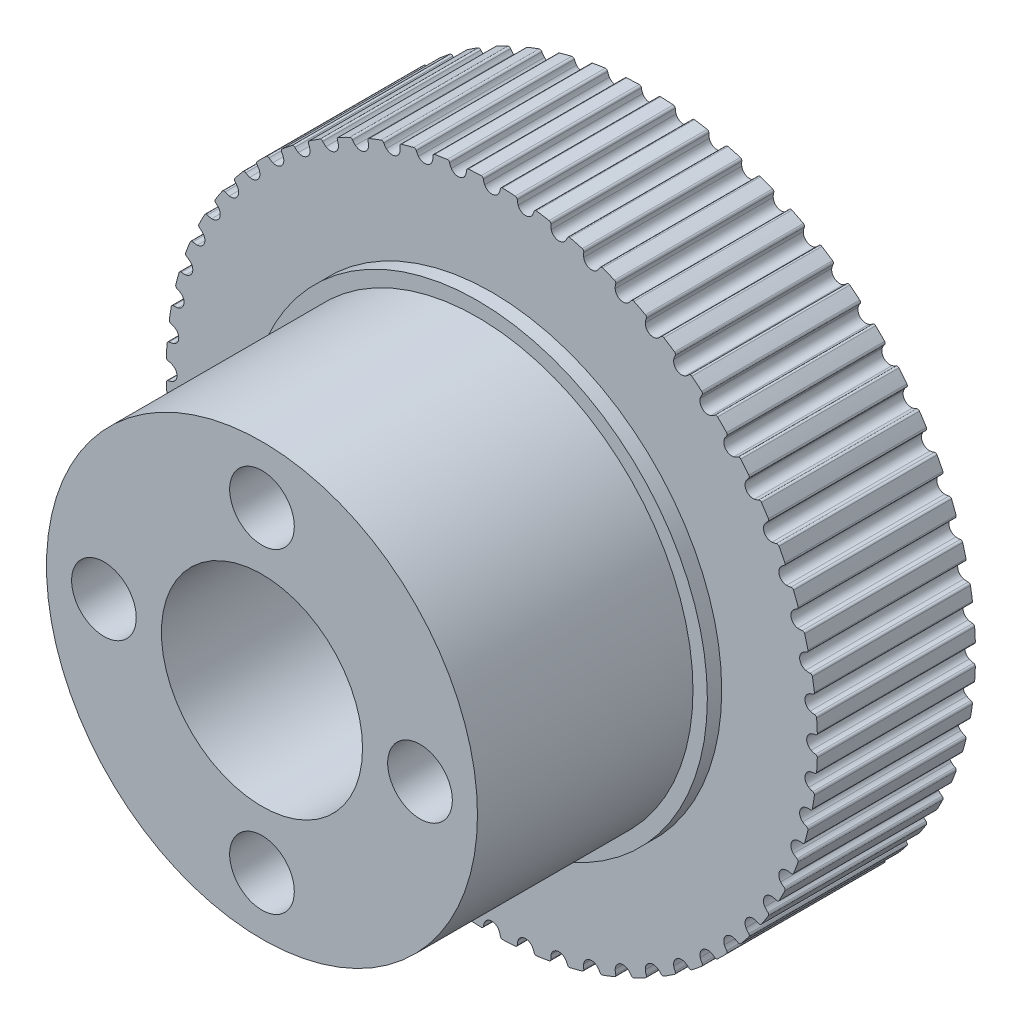
SolidWorks part; units mm, degrees
material "PLA+"
ref_plane "Front Plane" through (0, 0, 0) normal (0, 0, 1) x (1, 0, 0)
ref_plane "Top Plane" through (0, 0, 0) normal (0, 1, 0) x (1, 0, 0)
ref_plane "Right Plane" through (0, 0, 0) normal (1, 0, 0) x (0, 0, -1)
sketch "Sketch1" plane through (0, 0, 0) normal (0, 0, 1) x (1, 0, 0)
  circle A0 centre (0, 0) radius 22.9183 construction
  circle A1 centre (0, 0) radius 22.6643
  dimension "D1" = 45.8366
  dimension "D2" = 0.254
extrude "Boss-Extrude1" add sketch "Sketch1" along normal mid plane 11
sketch "Sketch2" plane through (0, 0, 5.5) normal (0, 0, 1) x (1, 0, 0)
  line L0 (0, 0) -> (0, 22.6643) construction
  line L1 (0, 22.6643) -> (0.4, 22.6643)
  circle A0 centre (0, 0) radius 22.6643 construction
  circle A1 centre (0.4, 22.6643) radius 1 construction
  circle A2 centre (0, 22.4693) radius 0.555 construction
  circle A3 centre (-0.7385, 22.5022) radius 0.15 construction
  circle A4 centre (0, 0) radius 22.6643 construction
  arc A5 (-0.7434, 22.6521) -> (-0.59, 22.5233) centre (-0.7385, 22.5022) cw
  arc A6 (-0.59, 22.5233) -> (-0.4989, 22.2261) centre (0.4, 22.6643) ccw
  arc A7 (-0.4989, 22.2261) -> (0.4989, 22.2261) centre (0, 22.4693) ccw
  arc A8 (0.59, 22.5233) -> (0.4989, 22.2261) centre (-0.4, 22.6643) cw
  arc A9 (0.7434, 22.6521) -> (0.59, 22.5233) centre (0.7385, 22.5022) ccw
  arc A10 (-0.7434, 22.6521) -> (0.7434, 22.6521) centre (0, 0) cw
  point P23 (0, 25.6998)
  circle M9 centre (0, 0) radius 22.6643
  dimension "D2" = 2
  dimension "D3" = 1.11
  dimension "D5" = 0.3
  dimension "D1" = 0.4
extrude "Cut-Extrude1" cut sketch "Sketch2" against normal through all contours A9 A5 A6 A7 A8 M9 region at (0, 22.3439, 5.5)
pattern_circular "CirPattern1" count 60 over 360 about axis through (0, 0, 5.5) along (0, 0, -1) of "Cut-Extrude1" reverse direction yes
sketch "Sketch3" plane through (0, 0, 5.5) normal (0, 0, 1) x (1, 0, 0)
  circle A0 centre (0, 0) radius 15
  dimension "D1" = 30
extrude "Boss-Extrude2" add sketch "Sketch3" along normal blind 16
sketch "Sketch5" plane through (0, 0, 21.5) normal (0, 0, 1) x (1, 0, 0)
  circle A0 centre (0, 0) radius 4
  dimension "D1" = 8
extrude "Cut-Extrude2" cut sketch "Sketch5" against normal through all
sketch "Sketch6" plane through (0, 0, 21.5) normal (0, 0, 1) x (1, 0, 0)
  line L0 (0, 11) -> (0, -11) construction
  line L1 (-11, 0) -> (11, 0) construction
  circle A0 centre (0, 0) radius 7
  circle A1 centre (0, 0) radius 11 construction
  circle A2 centre (0, 11) radius 2.25
  circle A3 centre (11, 0) radius 2.25
  circle A4 centre (0, -11) radius 2.25
  circle A5 centre (-11, 0) radius 2.25
  dimension "D1" = 14
  dimension "D2" = 22
  dimension "D3" = 4.5
  dimension "D4" = 4.5
  dimension "D5" = 4.5
  dimension "D6" = 4.5
extrude "Cut-Extrude3" cut sketch "Sketch6" against normal through all
sketch "Sketch7" plane through (0, 0, -5.5) normal (0, 0, -1) x (-1, 0, 0)
  circle A0 centre (0, 11) radius 3.6
  circle A1 centre (11, 0) radius 3.6
  circle A2 centre (-11, 0) radius 3.6
  circle A3 centre (0, -11) radius 3.6
  dimension "D1" = 7.2
  dimension "D2" = 7.2
  dimension "D3" = 7.2
  dimension "D4" = 7.2
extrude "Cut-Extrude4" cut sketch "Sketch7" against normal blind 5
sketch "Sketch8" plane through (0, 0, 5.5) normal (0, 0, 1) x (1, 0, 0)
  circle A2 centre (0, 0) radius 16
  circle A3 centre (0, 0) radius 16
  dimension "D1" = 1
extrude "Boss-Extrude3" add sketch "Sketch8" along normal blind 1
